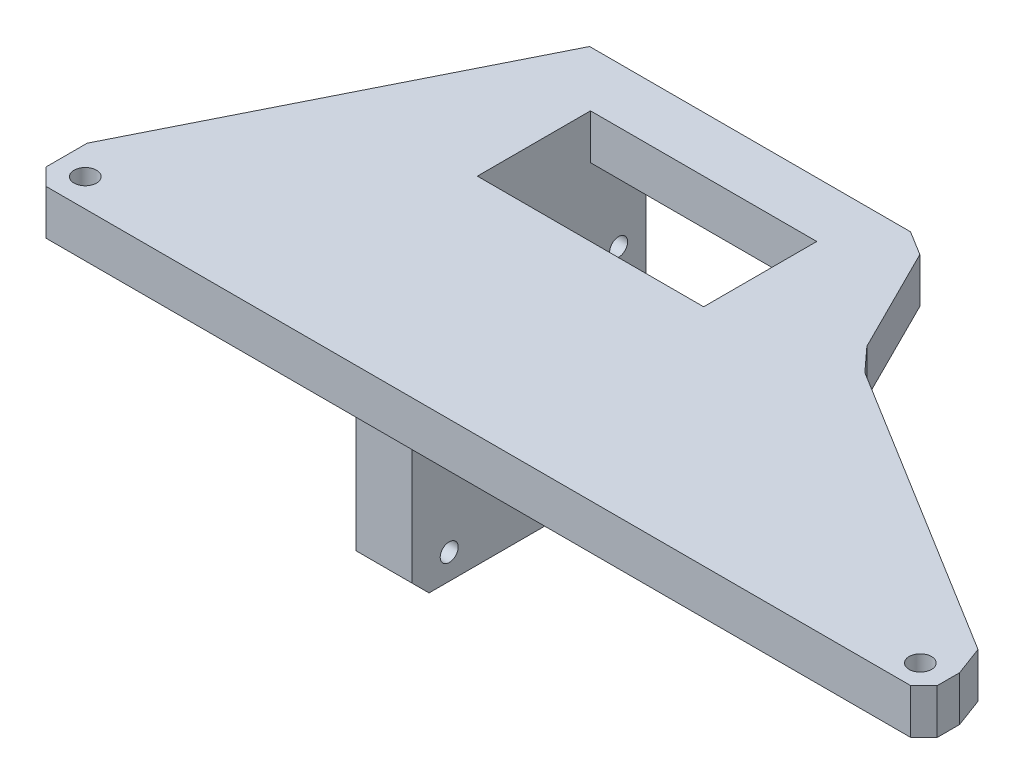
SolidWorks part; units mm, degrees
ref_plane "Alzado" through (0, 0, 0) normal (0, 0, 1) x (1, 0, 0)
ref_plane "Planta" through (0, 0, 0) normal (0, 1, 0) x (1, 0, 0)
ref_plane "Vista lateral" through (0, 0, 0) normal (1, 0, 0) x (0, 0, -1)
sketch "Croquis1" plane through (0, 0, 0) normal (0, 1, 0) x (1, 0, 0)
  line L1 (154, 0) -> (156.3961, 2.3528)
  line L2 (156.3961, 2.3528) -> (156.3961, 6.3528)
  line L3 (156.3961, 6.3528) -> (154.4465, 11.5749)
  line L4 (154.4465, 11.5749) -> (101.6651, 44.1989)
  line L5 (101.6651, 44.1989) -> (97.7729, 48.4584)
  line L6 (97.7729, 48.4584) -> (88.3473, 67.3137)
  line L7 (88.3473, 67.3137) -> (84.0091, 69.9952)
  line L8 (84.0091, 69.9952) -> (26.8414, 69.9952)
  line L9 (26.8414, 69.9952) -> (-2.9956, 10.3341)
  line L10 (-2.9956, 10.3341) -> (-2.9956, 3.0041)
  line L11 (-2.9956, 3.0041) -> (0, 0)
  line L13 (0, 0) -> (154, 0)
  line L14 (28.85, 60.15) -> (82.15, 60.15)
  line L15 (28.85, 40) -> (82.15, 40)
  line L16 (28.85, 40) -> (28.85, 60.15)
  line L18 (82.15, 40) -> (82.15, 60.15)
  line L19 (151.3979, 4.3528) -> (156.3961, 4.3528) construction
  line L20 (2, 5) -> (151.3979, 4.3528) construction
  line L21 (28.85, 40) -> (28.85, 4.8837) construction
  line L22 (82.15, 60.15) -> (91.9284, 60.15) construction
  circle A0 centre (2, 5) radius 2
  circle A3 centre (151.3979, 4.3528) radius 2
  point P21 (156.3961, 4.3528)
  dimension "D1" = 154
  dimension "D2" = 4.9981
  dimension "D24" = 4
  dimension "D25" = 4
  dimension "D3" = 4
  dimension "D4" = 149.3979
  dimension "D5" = 225.522
  dimension "D6" = 200.472
  dimension "D7" = 217.808
  dimension "D8" = 62.05
  dimension "D9" = 195.86
  dimension "D10" = 195.86
  dimension "D11" = 3.8922
  dimension "D12" = 9.4256
  dimension "D13" = 4.3382
  dimension "D14" = 57.1677
  dimension "D15" = 116.57
  dimension "D16" = 66.706
  dimension "D17" = 7.33
  dimension "D18" = 135.081
  dimension "D19" = 2.9956
  dimension "D20" = 26.85
  dimension "D21" = 35.1163
  dimension "D22" = 53.3
  dimension "D23" = 20.15
  dimension "D26" = 9.7784
extrude "Saliente-Extruir1" add sketch "Croquis1" along normal blind 8
sketch "Croquis2" plane through (0, 8, 0) normal (0, 1, 0) x (1, 0, 0)
  line L0 (28.85, 40) -> (82.15, 40) construction
  line L5 (26.8414, 69.9952) -> (36.8414, 69.9952)
  line L6 (82.15, 60.15) -> (77.15, 60.15)
  line L7 (82.15, 60.15) -> (82.15, 40)
  line L8 (82.15, 40) -> (77.15, 40)
  line L9 (77.15, 60.15) -> (77.15, 40)
  line L10 (84.0091, 69.9952) -> (26.8414, 69.9952) construction
  line L11 (36.8414, 69.9952) -> (36.8414, 28.3952)
  line L12 (26.8414, 69.9952) -> (26.8414, 28.3952)
  line L13 (26.8414, 28.3952) -> (36.8414, 28.3952)
  line M13 (84.0091, 69.9952) -> (26.8414, 69.9952)
  line M17 (28.85, 60.15) -> (82.15, 60.15)
  line M18 (82.15, 60.15) -> (82.15, 40)
  line M19 (82.15, 40) -> (28.85, 40)
  line M20 (28.85, 40) -> (28.85, 60.15)
  dimension "D1" = 10
  dimension "D2" = 41.6
  dimension "D3" = 5
extrude "Saliente-Extruir2" add sketch "Croquis2" against normal blind 60 contours L12 L13 L11 M19 M20 M17 M13 | L11 M17 M20 M19 region at (31.8414, 8, -69.5673) region at (32.8457, 8, -50.075)
extrude "Saliente-Extruir3" add sketch "Croquis2<4>" against normal blind 18 contours L9 M17 M19 M18 region at (79.65, 8, -50.075)
sketch "Croquis2<4>" plane through (0, 8, 0) normal (0, 1, 0) x (1, 0, 0) same geometry as "Croquis2"
sketch "Croquis3" plane through (82.15, 0, 0) normal (1, 0, 0) x (0, 0, -1)
  line L1 (50.075, -10) -> (50.075, -5) construction
  line L3 (60.15, -10) -> (40, -10) construction
  line L4 (59.15, -10) -> (60.15, -10)
  line L5 (50.075, -5) -> (40, -5) construction
  line L7 (40, -10) -> (40, 0) construction
  line L8 (60.15, -10) -> (60.15, -9)
  line L9 (60.15, -10) -> (60.15, 0) construction
  line L10 (40, -10) -> (40, -9)
  line L11 (40, -10) -> (41, -10)
  circle A0 centre (50.075, -5) radius 2
  arc A4 (40, -9) -> (41, -10) centre (41, -9) ccw
  arc A5 (59.15, -10) -> (60.15, -9) centre (59.15, -9) ccw
  point P18 (40, -10)
  point P21 (60.15, -10)
  dimension "D1" = 1
  dimension "D2" = 4
  dimension "D3" = 1
  dimension "D4" = 1
  dimension "D5" = 1
extrude "Cortar-Extruir1" cut sketch "Croquis3" against normal blind 107 contours A0 region at (82.15, -5, -50.075)
extrude "Cortar-Extruir2" cut sketch "Croquis3<3>" against normal blind 8
sketch "Croquis3<3>" plane through (82.15, 0, 0) normal (1, 0, 0) x (0, 0, -1) same geometry as "Croquis3"
sketch "Croquis5" plane through (36.8414, 0, 0) normal (1, 0, 0) x (0, 0, -1)
  line L0 (50.075, -5) -> (50.075, -31.5) construction
  line L1 (50.075, -31.5) -> (69.9952, -31.5) construction
  line L13 (69.9952, -52) -> (69.9952, 0) construction
  line L14 (69.9952, 0) -> (69.9952, -31.5) construction
  line L15 (28.3952, -52) -> (28.3952, -49)
  line L16 (34.985, -47.5) -> (65.165, -47.5) construction
  line L17 (34.985, -47.5) -> (34.985, -15.5) construction
  line L18 (34.985, -15.5) -> (65.165, -15.5) construction
  line L19 (65.165, -47.5) -> (65.165, -15.5) construction
  line L20 (50.075, -15.5) -> (50.075, -47.5) construction
  line L21 (34.985, -31.5) -> (65.165, -31.5) construction
  line L22 (28.3952, -52) -> (28.3952, 0) construction
  line L23 (28.3952, -49) -> (31.3952, -52)
  line L24 (69.9952, -52) -> (28.3952, -52) construction
  line L25 (31.3952, -52) -> (28.3952, -52)
  line L26 (69.9952, -52) -> (69.9952, -49)
  line L27 (69.9952, -49) -> (66.9952, -52)
  line L28 (66.9952, -52) -> (69.9952, -52)
  circle A0 centre (65.165, -15.5) radius 1.6
  circle A1 centre (50.075, -31.5) radius 12
  circle A2 centre (65.165, -47.5) radius 1.6
  circle A3 centre (34.985, -15.5) radius 1.6
  circle A4 centre (34.985, -47.5) radius 1.6
  dimension "D1" = 31.5
  dimension "D2" = 24
  dimension "D4" = 3.2
  dimension "D6" = 3.2
  dimension "D7" = 3.2
  dimension "D8" = 3.2
  dimension "D3" = 32
  dimension "D5" = 30.18
  dimension "D9" = 45
  dimension "D10" = 4.2426
  dimension "D11" = 4.2426
  dimension "D12" = 45
extrude "Cortar-Extruir3" cut sketch "Croquis5" against normal blind 59
